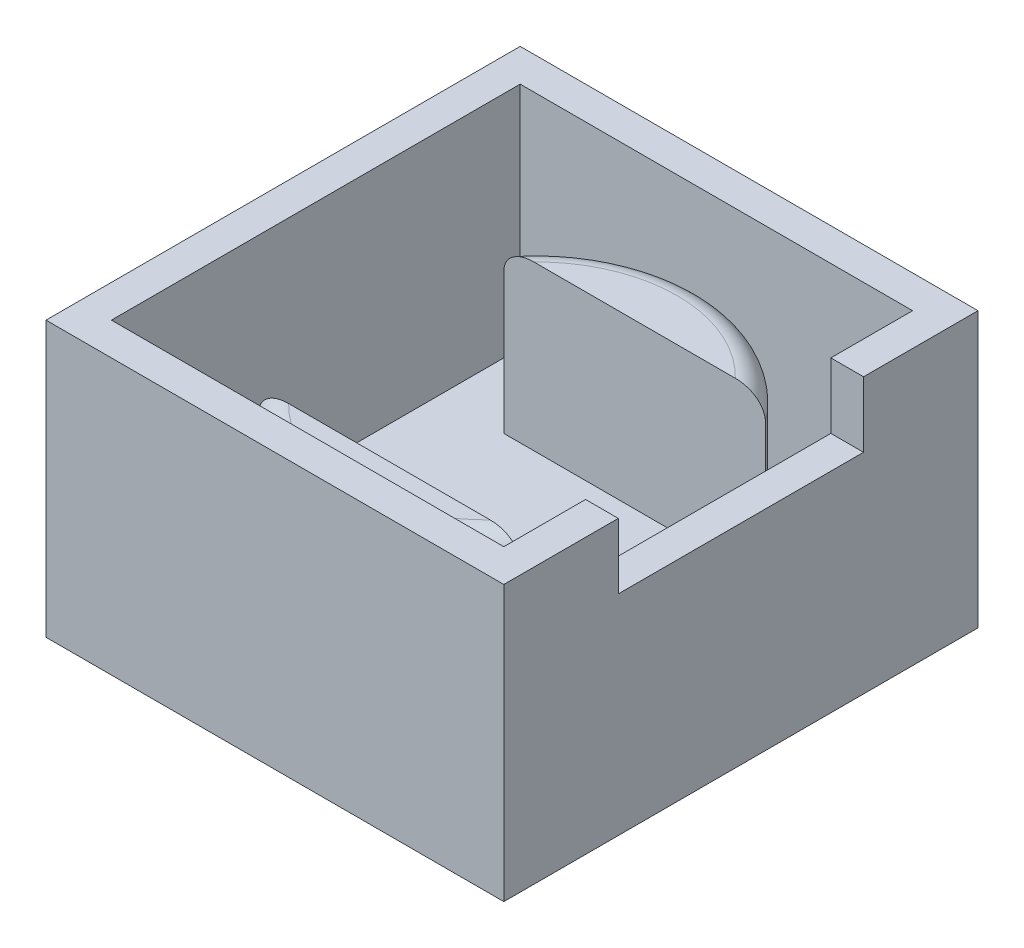
SolidWorks part; units mm, degrees
ref_plane "Front Plane" through (0, 0, 0) normal (0, 0, 1) x (1, 0, 0)
ref_plane "Top Plane" through (0, 0, 0) normal (0, 1, 0) x (1, 0, 0)
ref_plane "Right Plane" through (0, 0, 0) normal (1, 0, 0) x (0, 0, -1)
sketch "Sketch1" plane through (0, 0, 0) normal (0, 1, 0) x (1, 0, 0)
  line L1 (0, 0) -> (30.48, 0)
  line L2 (0, 0) -> (0, 31.75)
  line L3 (0, 31.75) -> (30.48, 31.75)
  line L4 (30.48, 0) -> (30.48, 31.75)
  dimension "D1" = 31.75
  dimension "D2" = 30.48
extrude "Boss-Extrude1" add sketch "Sketch1" along normal blind 3.556
sketch "Sketch2" plane through (0, 3.556, 0) normal (0, 1, 0) x (1, 0, 0)
  line L0 (0, 31.75) -> (0, 0) construction
  line L1 (0, 25.4) -> (30.48, 25.4)
  line L2 (0, 25.4) -> (0, 6.35)
  line L3 (0, 6.35) -> (30.48, 6.35)
  line L4 (30.48, 25.4) -> (30.48, 6.35)
  line L5 (30.48, 0) -> (30.48, 31.75) construction
  line L6 (30.48, 25.4) -> (30.48, 31.75) construction
  line L7 (30.48, 0) -> (30.48, 6.35) construction
  line L8 (0, 15.875) -> (30.48, 15.875) construction
  arc A0 (5.08, 25.4) -> (25.4, 25.4) centre (15.24, 17.78) cw
  arc A1 (5.08, 6.35) -> (25.4, 6.35) centre (15.24, 13.97) ccw
  dimension "D1" = 19.05
  dimension "D2" = 7.62
extrude "Boss-Extrude2" add sketch "Sketch2" along normal blind 12.7 contours L3 A1 | A0 L1 region at (15.24, 3.556, -27.4714) region at (15.24, 3.556, -4.2786)
sketch "Sketch4" plane through (0, 3.556, 0) normal (0, 1, 0) x (1, 0, 0)
  line L0 (0, 31.75) -> (0, 0) construction
  line L1 (-1.778, 33.528) -> (67.818, 33.528)
  line L2 (-1.778, 33.528) -> (-1.778, -39.878)
  line L3 (-1.778, -39.878) -> (67.818, -39.878)
  line L4 (67.818, 33.528) -> (67.818, -39.878)
  line L5 (30.48, 31.75) -> (0, 31.75) construction
  line L7 (0, 31.75) -> (66.04, 31.75)
  line L8 (0, 31.75) -> (0, -38.1)
  line L9 (0, -38.1) -> (66.04, -38.1)
  line L10 (66.04, 31.75) -> (66.04, -38.1)
  line L12 (17.145, -38.1) -> (17.145, -7.62)
  line L13 (17.145, -7.62) -> (48.895, -7.62)
  line L14 (48.895, -7.62) -> (48.895, -38.1)
  line L15 (33.02, -38.1) -> (33.02, 16.283) construction
  line M12 (0, 31.75) -> (0, 0)
  line M13 (0, 0) -> (30.48, 0)
  line M14 (30.48, 0) -> (30.48, 31.75)
  line M15 (30.48, 31.75) -> (0, 31.75)
  dimension "D1" = 69.596
  dimension "D2" = 73.406
  dimension "D3" = 1.778
  dimension "D4" = 1.778
  dimension "D5" = 1.778
  dimension "D6" = 1.778
  dimension "D7" = 15.875
  dimension "D8" = 15.875
  dimension "D9" = 30.48
extrude "Boss-Extrude3" add sketch "Sketch4" against normal blind 3.556 contours L4 L1 L2 L3 L7 L10 L9 L8 M12 M15 | L13 L14 L9 L10 L7 L8 L12 M14 M13 | L15 L9 L14 L13 | L9 L15 L13 L12 region at (33.02, 3.556, -32.5165) region at (39.4465, 3.556, 2.9455) region at (25.0825, 3.556, 22.86) region at (40.9575, 3.556, 22.86)
sketch "Sketch8" plane through (0, 3.556, 0) normal (0, 1, 0) x (1, 0, 0)
  line L0 (0, 31.75) -> (0, 27.178)
  line L1 (0, 0) -> (0, 31.75) construction
  line L2 (0, 27.178) -> (0, 4.572)
  line L3 (-1.778, 27.178) -> (-1.778, 33.528)
  line L4 (-1.778, 33.528) -> (32.258, 33.528)
  line L5 (32.258, 33.528) -> (32.258, -1.778)
  line L6 (32.258, -1.778) -> (-1.778, -1.778)
  line L7 (-1.778, -1.778) -> (-1.778, 4.572)
  line L8 (-1.778, 4.572) -> (-1.778, 27.178)
  line L9 (0, 4.572) -> (0, 0)
  line L10 (0, 0) -> (30.48, 0)
  line L11 (30.48, 0) -> (30.48, 31.75)
  line L12 (30.48, 31.75) -> (0, 31.75)
  dimension "D1" = 1.778
  dimension "D2" = 1.778
  dimension "D3" = 1.778
  dimension "D4" = 1.778
  dimension "D5" = 1.778
  dimension "D6" = 6.35
  dimension "D7" = 6.35
extrude "Boss-Extrude5" add sketch "Sketch8" along normal blind 12.7
ref_plane "Plane2" through (0, 0, 3.175) normal (0, 0, -1) x (-1, 0, 0)
ref_plane "Plane1" through (33.02, 0, 0) normal (1, 0, 0) x (0, 0, -1)
mirror "Mirror1" about plane through (0, 0, 3.175) normal (0, 0, -1) of "Boss-Extrude5"
mirror "Mirror2" about plane through (33.02, 0, 0) normal (1, 0, 0) of "Mirror1"
mirror "Mirror3" about plane through (0, 0, 3.175) normal (0, 0, -1) of "Boss-Extrude2"
mirror "Mirror4" about plane through (33.02, 0, 0) normal (1, 0, 0) of "Mirror3"
fillet "Fillet5" radius 1.778 8 edges at (50.8, 16.256, 36.83) (15.24, 16.256, 36.83) (15.24, 16.256, 7.62) (15.24, 16.256, -1.27) (15.24, 16.256, -30.48) (50.8, 16.256, -30.48) (50.8, 16.256, -1.27) (50.8, 16.256, 7.62)
sketch "Sketch9" plane through (0, 16.256, 0) normal (0, 1, 0) x (1, 0, 0)
  line L1 (32.258, 33.528) -> (33.782, 33.528)
  line L2 (32.258, 33.528) -> (32.258, -39.878)
  line L3 (32.258, -39.878) -> (33.782, -39.878)
  line L4 (33.782, 33.528) -> (33.782, -39.878)
  line L5 (-1.778, -1.778) -> (67.818, -1.778)
  line L6 (-1.778, -1.778) -> (-1.778, -4.572)
  line L7 (-1.778, -4.572) -> (67.818, -4.572)
  line L8 (67.818, -1.778) -> (67.818, -4.572)
  line M47 (-1.778, -1.778) -> (32.258, -1.778)
  line M48 (32.258, -1.778) -> (32.258, 33.528)
extrude "Boss-Extrude7" add sketch "Sketch9" against normal up to body contours L5 L4 L1 M48 | L7 L2 L3 L4 | L2 L7 L4 L5 | L8 L5 L4 L7 | L6 L7 L2 M47 region at (33.02, 16.256, -15.875) region at (33.02, 16.256, 3.175) region at (15.24, 16.256, 3.175) region at (50.8, 16.256, 3.175) region at (33.02, 16.256, 22.225)
sketch "Sketch10" plane through (0, 16.256, 0) normal (0, 1, 0) x (1, 0, 0)
  line L0 (67.818, -4.572) -> (33.782, -4.572)
  line L1 (67.818, -39.878) -> (67.818, 33.528) construction
  line L2 (33.782, -4.572) -> (33.782, -39.878)
  line L3 (67.818, -39.878) -> (-1.778, -39.878) construction
  line L4 (33.782, -39.878) -> (-10.0613, -39.878)
  line L5 (-10.0613, -39.878) -> (-10.0613, 34.6908)
  line L6 (-10.0613, 34.6908) -> (71.0188, 34.6908)
  line L7 (71.0188, 34.6908) -> (71.0188, -4.572)
  line L8 (71.0188, -4.572) -> (67.818, -4.572)
  line L9 (35.56, -6.35) -> (35.56, -38.1) construction
  line L10 (66.04, -6.35) -> (35.56, -6.35) construction
  dimension "D1" = 1.778
  dimension "D2" = 1.778
extrude "Cut-Extrude1" cut sketch "Sketch10" against normal through all
sketch "Sketch11" plane through (0, 16.256, 0) normal (0, 1, 0) x (1, 0, 0)
  line L0 (33.02, -3.81) -> (33.02, -40.64)
  line L1 (33.782, -4.572) -> (67.818, -4.572)
  line L2 (33.782, -4.572) -> (33.782, -39.878)
  line L3 (33.782, -39.878) -> (67.818, -39.878)
  line L4 (67.818, -4.572) -> (67.818, -39.878)
  line L5 (33.02, -40.64) -> (68.58, -40.64)
  line L6 (68.58, -3.81) -> (68.58, -40.64)
  line L7 (33.02, -3.81) -> (68.58, -3.81)
  dimension "D1" = 0.762
extrude "Boss-Extrude8" add sketch "Sketch11" against normal up to surface (16.256 mm away) up to face at (50.8, 0, 22.225)
sketch "Sketch12" plane through (0, 16.256, 0) normal (0, 1, 0) x (1, 0, 0)
  line L0 (66.04, -12.7) -> (68.58, -12.7)
  line L1 (35.56, -6.35) -> (66.04, -6.35)
  line L2 (35.56, -6.35) -> (35.56, -38.1)
  line L3 (35.56, -38.1) -> (66.04, -38.1)
  line L4 (66.04, -6.35) -> (66.04, -12.7)
  line L5 (68.58, -40.64) -> (33.02, -40.64)
  line L6 (68.58, -40.64) -> (68.58, -31.75)
  line L7 (68.58, -3.81) -> (33.02, -3.81)
  line L8 (33.02, -40.64) -> (33.02, -3.81)
  line L9 (66.04, -31.75) -> (68.58, -31.75)
  line L10 (66.04, -22.225) -> (68.58, -22.225) construction
  line L11 (66.04, -31.75) -> (66.04, -38.1)
  line L12 (68.58, -12.7) -> (68.58, -3.81)
  dimension "D1" = 19.05
  dimension "D2" = 9.525
extrude "Boss-Extrude9" add sketch "Sketch12" along normal blind 5.08
